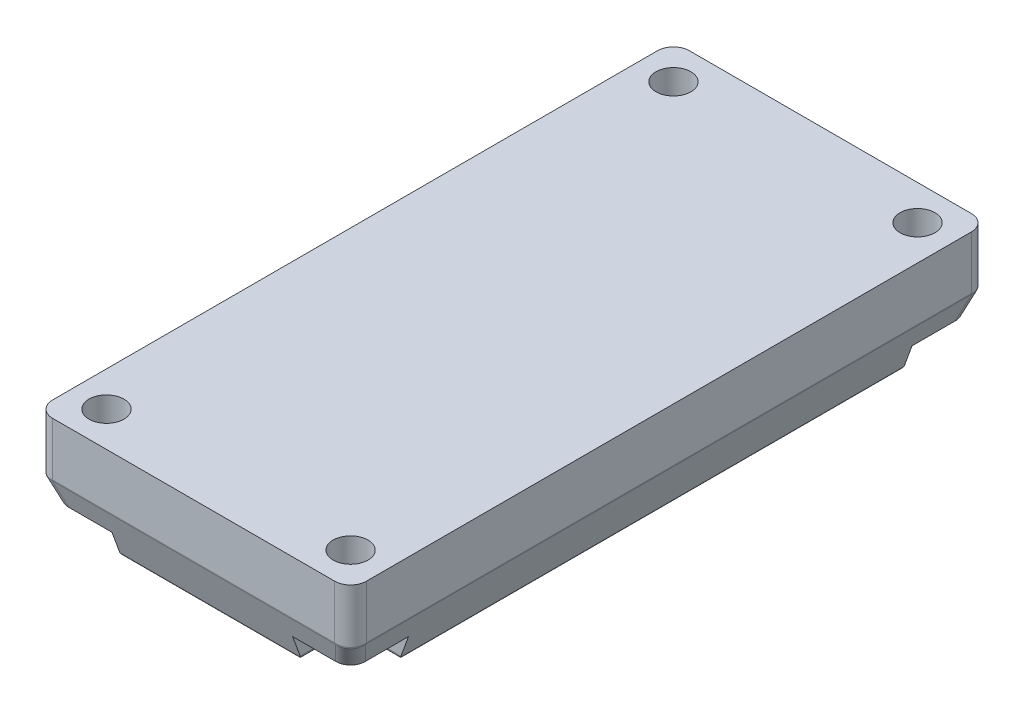
SolidWorks part; units mm, degrees
material "PC High Viscosity"
ref_plane "Front Plane" through (0, 0, 0) normal (0, 0, 1) x (1, 0, 0)
ref_plane "Top Plane" through (0, 0, 0) normal (0, 1, 0) x (1, 0, 0)
ref_plane "Right Plane" through (0, 0, 0) normal (1, 0, 0) x (0, 0, -1)
sketch "BaseS" plane through (0, 0, 0) normal (0, 1, 0) x (1, 0, 0)
  line L0 (-9.9, 20.085) -> (9.9, 20.085)
  line L1 (-9.9, 20.085) -> (-9.9, -20.085)
  line L2 (-9.9, -20.085) -> (9.9, -20.085)
  line L3 (9.9, 20.085) -> (9.9, -20.085)
  line L4 (-9.9, 20.085) -> (9.9, -20.085) construction
  line L5 (-9.9, -20.085) -> (9.9, 20.085) construction
  point P0 (0, 0)
  dimension "D1" = 19.8
  dimension "D2" = 40.17
extrude "BASE" add sketch "BaseS" along normal blind 6.4
sketch "HoleSideCutsS" plane through (0, 0, 0) normal (0, -1, 0) x (1, 0, 0)
  line L0 (-5.7, 17.685) -> (-5.7, 20.085)
  line L1 (-7.5, 15.885) -> (-9.9, 15.885)
  line L2 (-5.7, 20.085) -> (-9.9, 20.085)
  line L3 (-9.9, 20.085) -> (-9.9, 15.885)
  line L4 (-9.9, 20.085) -> (9.9, 20.085) construction
  line L5 (-9.9, -20.085) -> (-9.9, 20.085) construction
  arc A0 (-7.5, 15.885) -> (-5.7, 17.685) centre (-7.5, 17.685) ccw
  dimension "D3" = 3.6
  dimension "D1" = 4.2
extrude "HOLE SIDE CUTS" cut sketch "HoleSideCutsS" against normal blind 1.5
hole_wizard "M2 Clearance Hole1" positions "Sketch3" profile "Sketch4" hole size "M2" standard "ANSI Metric" end condition through all
sketch "Sketch3" plane through (0, 1.5, 0) normal (0, -1, 0) x (-1, 0, 0)
  line L0 (9.9, -20.085) -> (9.9, -15.885) construction
  line L1 (5.7, -20.085) -> (9.9, -20.085) construction
  point P0 (7.7, -17.885)
  dimension "D1" = 2.2
  dimension "D2" = 2.2
sketch "Sketch4" plane through (-7.7, 1.5, 17.885) normal (1, 0, 0) x (0, 0, -1)
  line L0 (0, 0) -> (0, 4.9)
  line L1 (0, 4.9) -> (1.1, 4.9)
  line L2 (1.1, 4.9) -> (1.1, 0)
  line L5 (1.1, 0) -> (0, 0)
  line L11 (0, -6.35) -> (0, 107.95) construction
  dimension "Thru Hole Dia." = 2.2
  dimension "Thru Hole Depth" = 4.9
mirror "HOLE FEATURES HM" about plane through (0, 0, 0) normal (1, 0, 0) of "M2 Clearance Hole1", "HOLE SIDE CUTS"
mirror "HOLE FEATURE VM" about plane through (0, 0, 0) normal (0, 0, 1) of "HOLE FEATURES HM", "HOLE SIDE CUTS", "M2 Clearance Hole1"
sketch "SideChamfer1S" plane through (0, 0, 0) normal (0, 0, 1) x (1, 0, 0)
  line L0 (9.9, 3) -> (9.9, 0)
  line L1 (9.9, 6.4) -> (9.9, 1.5) construction
  line L2 (9.9, 0) -> (8.8081, 0)
  line L3 (9.9, 0) -> (7.5, 0) construction
  line L4 (8.8081, 0) -> (9.9, 3)
  dimension "D1" = 3
  dimension "D2" = 20
extrude "SIDE CHAMFER 1" cut sketch "SideChamfer1S" against normal through all both and the other way through all
mirror "SC1 HM" about plane through (0, 0, 0) normal (1, 0, 0) of "SIDE CHAMFER 1"
sketch "SideChamfer2S" plane through (0, 0, 0) normal (1, 0, 0) x (0, 0, -1)
  line L0 (20.085, 3) -> (20.085, 0)
  line L1 (20.085, 6.4) -> (20.085, 3) construction
  line L2 (20.085, 0) -> (18.9931, 0)
  line L4 (18.9931, 0) -> (20.085, 3)
  dimension "D1" = 3
  dimension "D2" = 20
extrude "SIDE CHAMFER 2" cut sketch "SideChamfer2S" against normal through all both and the other way through all
mirror "SC2 VM" about plane through (0, 0, 0) normal (0, 0, 1) of "SIDE CHAMFER 2"
fillet "BASE F" radius 1 8 edges at (-9.627, 2.25, -19.812) (-9.9, 4.7, -20.085) (9.627, 2.25, -19.812) (9.9, 4.7, -20.085) (-9.627, 2.25, 19.812) (-9.9, 4.7, 20.085) (9.627, 2.25, 19.812) (9.9, 4.7, 20.085)
fillet "BASE BOTTOM F" radius 0.2 32 edges at (9.8996, 2.9988, -19.1143) (9.6071, 2.9341, -19.7921) (8.9293, 2.9988, -20.0846) (0, 3, -20.085) (-8.9293, 2.9988, -20.0846) (-9.6071, 2.9341, -19.7921) (-9.8996, 2.9988, -19.1143) (-9.9, 3, 0) (-9.8996, 2.9988, 19.1143) (-9.6071, 2.9341, 19.7921) (-8.9293, 2.9988, 20.0846) (0, 3, 20.085) (8.9293, 2.9988, 20.0846) (9.6071, 2.9341, 19.7921) (9.8996, 2.9988, 19.1143) (5.7, 0, 18.339) (6.2272, 0, 16.4122) (8.154, 0, 15.885) (8.8081, 0, 0) (8.154, 0, -15.885) (6.2272, 0, -16.4122) (5.7, 0, -18.339) (0, 0, -18.9931) (-5.7, 0, -18.339) (-6.2272, 0, -16.4122) (-8.154, 0, -15.885) (-8.8081, 0, 0) (-8.154, 0, 15.885) (-6.2272, 0, 16.4122) (-5.7, 0, 18.339) (0, 0, 18.9931) (9.9, 3, 0)
